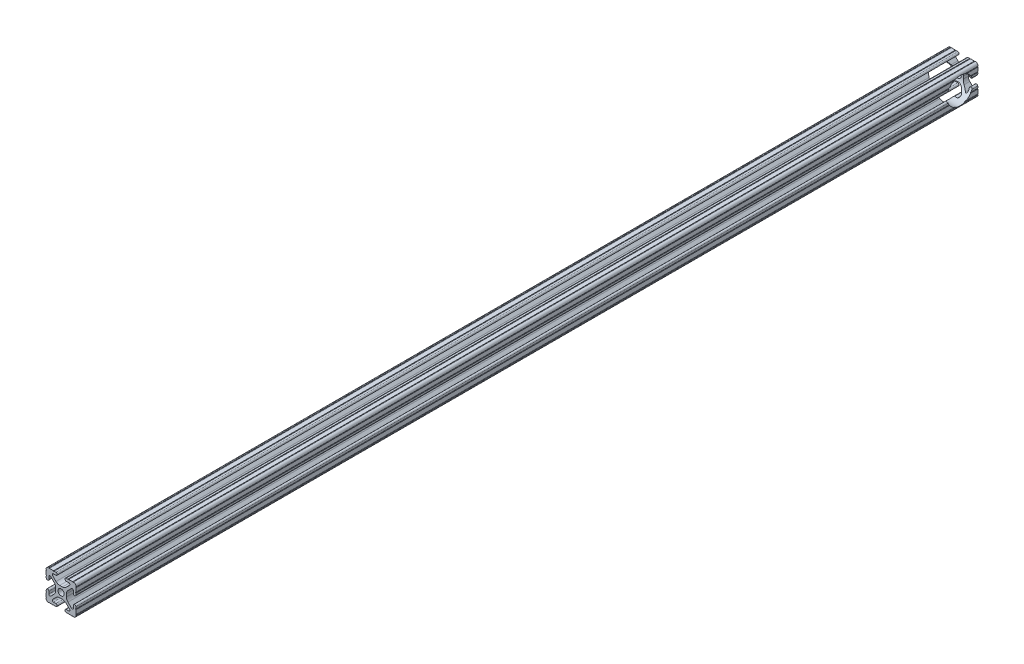
SolidWorks part; units mm, degrees
ref_plane "Front Plane" through (0, 0, 0) normal (0, 0, 1) x (1, 0, 0)
ref_plane "Top Plane" through (0, 0, 0) normal (0, 1, 0) x (1, 0, 0)
ref_plane "Right Plane" through (0, 0, 0) normal (1, 0, 0) x (0, 0, -1)
sketch "Sketch1" plane through (0, 0, 0) normal (0, 0, 1) x (1, 0, 0)
  line L0 (0, 12.7) -> (-12.7814, 12.7) construction
  line L1 (-4.5085, 0) -> (-4.5085, 2.9459)
  line L2 (-6.0437, 12.5461) -> (-10.0976, 12.6876) construction
  line L3 (-11.5616, 12.4229) -> (-4.3159, 12.1699) construction
  line L4 (-6.4364, 10.3486) -> (-6.3592, 12.5571) construction
  line L6 (-2.9459, 4.5085) -> (0, 4.5085)
  line L7 (0, 0) -> (0, 12.7) construction
  line L8 (0, 0) -> (-12.7814, 0) construction
  line L9 (0.7813, 0.7813) -> (-0.7813, -0.7813) construction
  line L10 (-2.9459, 4.5085) -> (-7.1484, 8.711)
  line L11 (-4.5085, 2.9459) -> (-8.711, 7.1484)
  line L13 (0, 0) -> (-12.7814, 12.7814) construction
  line L14 (-10.4131, 12.6987) -> (-4.3048, 12.4853)
  line L15 (-4.3048, 12.4853) -> (-4.382, 10.2769) construction
  line L16 (-4.382, 10.2769) -> (-6.4364, 10.3486)
  line L17 (-12.6987, 10.4131) -> (-12.4853, 4.3048)
  line L18 (-10.2769, 4.382) -> (-10.3486, 6.4364)
  circle A0 centre (0, 0) radius 2.6035
  arc A1 (-4.382, 10.2769) -> (-4.3048, 12.4853) centre (-4.3434, 11.3811) ccw
  arc A2 (-7.1484, 8.711) -> (-6.4364, 10.3486) centre (-6.4698, 9.3896) cw
  arc A3 (-8.711, 7.1484) -> (-10.3486, 6.4364) centre (-9.3896, 6.4698) ccw
  arc A4 (-10.2769, 4.382) -> (-12.4853, 4.3048) centre (-11.3811, 4.3434) cw
  arc A5 (-10.4131, 12.6987) -> (-12.6987, 10.4131) centre (-10.4902, 10.4902) ccw
  arc A6 (-10.4131, 12.6987) -> (-9.7821, 12.6766) centre (-10.0976, 12.6876) ccw
  arc A7 (-6.3592, 12.5571) -> (-5.7282, 12.5351) centre (-6.0437, 12.5461) ccw
  arc A8 (-12.5571, 6.3592) -> (-12.5351, 5.7282) centre (-12.5461, 6.0437) cw
  arc A9 (-12.6987, 10.4131) -> (-12.6766, 9.7821) centre (-12.6876, 10.0976) cw
  dimension "D1" = 5.207
  dimension "D5" = 14.859
  dimension "D9" = 2
  dimension "D2" = 25.4
  dimension "D12" = 0.6314
  dimension "D10" = 2.2098
  dimension "D3" = 9.017
  dimension "D4" = 9.017
  dimension "D6" = 25.4
  dimension "D7" = 6.477
  dimension "D8" = 2.2098
  dimension "D11" = 12.7
sketch "Sketch3" plane through (0, 0, 0) normal (0, 0, 1) x (1, 0, 0)
  line L0 (-2.9459, 4.5085) -> (0, 4.5085) construction
  line L1 (-2.9459, 4.5085) -> (-7.1484, 8.711) construction
  line L2 (-4.382, 10.2769) -> (-6.4364, 10.3486) construction
  line L3 (-10.4131, 12.6987) -> (-4.3048, 12.4853) construction
  line L4 (-4.5085, 0) -> (-4.5085, 2.9459) construction
  line L5 (-4.5085, 2.9459) -> (-8.711, 7.1484) construction
  line L6 (-10.2769, 4.382) -> (-10.3486, 6.4364) construction
  line L7 (-12.6987, 10.4131) -> (-12.4853, 4.3048) construction
  line L8 (-1.1153, 4.5085) -> (1.1153, 4.5085)
  line L9 (-4.2404, 5.803) -> (-7.1484, 8.711)
  line L10 (-4.382, 10.2769) -> (-6.4364, 10.3486)
  line L11 (-9.7821, 12.6766) -> (-6.3592, 12.5571)
  line L12 (-4.5085, -1.1153) -> (-4.5085, 1.1153)
  line L13 (-5.803, 4.2404) -> (-8.711, 7.1484)
  line L14 (-10.2769, 4.382) -> (-10.3486, 6.4364)
  line L15 (-12.6766, 9.7821) -> (-12.5571, 6.3592)
  line L16 (-5.7282, 12.5351) -> (-4.3048, 12.4853)
  line L17 (-12.5351, 5.7282) -> (-12.4853, 4.3048)
  line L18 (0, 0) -> (0, 12.7) construction
  line L19 (0, 0) -> (-12.7814, 0) construction
  line L20 (12.5351, 5.7282) -> (12.4853, 4.3048)
  line L21 (5.7282, 12.5351) -> (4.3048, 12.4853)
  line L22 (12.6766, 9.7821) -> (12.5571, 6.3592)
  line L23 (10.2769, 4.382) -> (10.3486, 6.4364)
  line L24 (5.803, 4.2404) -> (8.711, 7.1484)
  line L25 (4.5085, -1.1153) -> (4.5085, 1.1153)
  line L26 (9.7821, 12.6766) -> (6.3592, 12.5571)
  line L27 (4.382, 10.2769) -> (6.4364, 10.3486)
  line L28 (4.2404, 5.803) -> (7.1484, 8.711)
  line L29 (4.2404, -5.803) -> (7.1484, -8.711)
  line L30 (4.382, -10.2769) -> (6.4364, -10.3486)
  line L31 (9.7821, -12.6766) -> (6.3592, -12.5571)
  line L32 (5.803, -4.2404) -> (8.711, -7.1484)
  line L33 (10.2769, -4.382) -> (10.3486, -6.4364)
  line L34 (12.6766, -9.7821) -> (12.5571, -6.3592)
  line L35 (5.7282, -12.5351) -> (4.3048, -12.4853)
  line L36 (12.5351, -5.7282) -> (12.4853, -4.3048)
  line L37 (-12.5351, -5.7282) -> (-12.4853, -4.3048)
  line L38 (-5.7282, -12.5351) -> (-4.3048, -12.4853)
  line L39 (-12.6766, -9.7821) -> (-12.5571, -6.3592)
  line L40 (-10.2769, -4.382) -> (-10.3486, -6.4364)
  line L41 (-5.803, -4.2404) -> (-8.711, -7.1484)
  line L42 (-9.7821, -12.6766) -> (-6.3592, -12.5571)
  line L43 (-4.382, -10.2769) -> (-6.4364, -10.3486)
  line L44 (-4.2404, -5.803) -> (-7.1484, -8.711)
  line L45 (-1.1153, -4.5085) -> (1.1153, -4.5085)
  arc A0 (-10.4131, 12.6987) -> (-9.7821, 12.6766) centre (-10.0976, 12.6876) ccw construction
  arc A1 (-6.4364, 10.3486) -> (-7.1484, 8.711) centre (-6.4698, 9.3896) ccw construction
  arc A2 (-4.382, 10.2769) -> (-4.3048, 12.4853) centre (-4.3434, 11.3811) ccw construction
  arc A3 (-8.711, 7.1484) -> (-10.3486, 6.4364) centre (-9.3896, 6.4698) ccw construction
  arc A4 (-12.4853, 4.3048) -> (-10.2769, 4.382) centre (-11.3811, 4.3434) ccw construction
  arc A5 (-6.3592, 12.5571) -> (-5.7282, 12.5351) centre (-6.0437, 12.5461) ccw construction
  arc A6 (-10.4131, 12.6987) -> (-12.6987, 10.4131) centre (-10.4902, 10.4902) ccw construction
  arc A7 (-12.6766, 9.7821) -> (-12.6987, 10.4131) centre (-12.6876, 10.0976) ccw construction
  arc A8 (-12.5351, 5.7282) -> (-12.5571, 6.3592) centre (-12.5461, 6.0437) ccw construction
  arc A9 (-10.4131, 12.6987) -> (-9.7821, 12.6766) centre (-10.0976, 12.6876) ccw
  arc A10 (-6.4364, 10.3486) -> (-7.1484, 8.711) centre (-6.4698, 9.3896) ccw
  arc A11 (-4.382, 10.2769) -> (-4.3048, 12.4853) centre (-4.3434, 11.3811) ccw
  arc A12 (-8.711, 7.1484) -> (-10.3486, 6.4364) centre (-9.3896, 6.4698) ccw
  arc A13 (-12.4853, 4.3048) -> (-10.2769, 4.382) centre (-11.3811, 4.3434) ccw
  arc A14 (-6.3592, 12.5571) -> (-5.7282, 12.5351) centre (-6.0437, 12.5461) ccw
  arc A15 (-10.4131, 12.6987) -> (-12.6987, 10.4131) centre (-10.4902, 10.4902) ccw
  arc A16 (-12.6766, 9.7821) -> (-12.6987, 10.4131) centre (-12.6876, 10.0976) ccw
  arc A17 (-12.5351, 5.7282) -> (-12.5571, 6.3592) centre (-12.5461, 6.0437) ccw
  arc A18 (-1.1153, 4.5085) -> (-4.2404, 5.803) centre (-1.1153, 8.9281) cw
  arc A19 (4.5085, 1.1153) -> (5.803, 4.2404) centre (8.9281, 1.1153) cw
  arc A20 (1.1153, 4.5085) -> (4.2404, 5.803) centre (1.1153, 8.9281) ccw
  arc A21 (-4.5085, 1.1153) -> (-5.803, 4.2404) centre (-8.9281, 1.1153) ccw
  arc A22 (12.5351, 5.7282) -> (12.5571, 6.3592) centre (12.5461, 6.0437) cw
  arc A23 (12.6766, 9.7821) -> (12.6987, 10.4131) centre (12.6876, 10.0976) cw
  arc A24 (10.4131, 12.6987) -> (12.6987, 10.4131) centre (10.4902, 10.4902) cw
  arc A25 (6.3592, 12.5571) -> (5.7282, 12.5351) centre (6.0437, 12.5461) cw
  arc A26 (12.4853, 4.3048) -> (10.2769, 4.382) centre (11.3811, 4.3434) cw
  arc A27 (8.711, 7.1484) -> (10.3486, 6.4364) centre (9.3896, 6.4698) cw
  arc A28 (4.382, 10.2769) -> (4.3048, 12.4853) centre (4.3434, 11.3811) cw
  arc A29 (6.4364, 10.3486) -> (7.1484, 8.711) centre (6.4698, 9.3896) cw
  arc A30 (10.4131, 12.6987) -> (9.7821, 12.6766) centre (10.0976, 12.6876) cw
  arc A31 (10.4131, -12.6987) -> (9.7821, -12.6766) centre (10.0976, -12.6876) ccw
  arc A32 (6.4364, -10.3486) -> (7.1484, -8.711) centre (6.4698, -9.3896) ccw
  arc A33 (4.382, -10.2769) -> (4.3048, -12.4853) centre (4.3434, -11.3811) ccw
  arc A34 (8.711, -7.1484) -> (10.3486, -6.4364) centre (9.3896, -6.4698) ccw
  arc A35 (12.4853, -4.3048) -> (10.2769, -4.382) centre (11.3811, -4.3434) ccw
  arc A36 (6.3592, -12.5571) -> (5.7282, -12.5351) centre (6.0437, -12.5461) ccw
  arc A37 (10.4131, -12.6987) -> (12.6987, -10.4131) centre (10.4902, -10.4902) ccw
  arc A38 (12.6766, -9.7821) -> (12.6987, -10.4131) centre (12.6876, -10.0976) ccw
  arc A39 (12.5351, -5.7282) -> (12.5571, -6.3592) centre (12.5461, -6.0437) ccw
  arc A40 (-4.5085, -1.1153) -> (-5.803, -4.2404) centre (-8.9281, -1.1153) cw
  arc A41 (1.1153, -4.5085) -> (4.2404, -5.803) centre (1.1153, -8.9281) cw
  arc A42 (4.5085, -1.1153) -> (5.803, -4.2404) centre (8.9281, -1.1153) ccw
  arc A43 (-1.1153, -4.5085) -> (-4.2404, -5.803) centre (-1.1153, -8.9281) ccw
  arc A44 (-12.5351, -5.7282) -> (-12.5571, -6.3592) centre (-12.5461, -6.0437) cw
  arc A45 (-12.6766, -9.7821) -> (-12.6987, -10.4131) centre (-12.6876, -10.0976) cw
  arc A46 (-10.4131, -12.6987) -> (-12.6987, -10.4131) centre (-10.4902, -10.4902) cw
  arc A47 (-6.3592, -12.5571) -> (-5.7282, -12.5351) centre (-6.0437, -12.5461) cw
  arc A48 (-12.4853, -4.3048) -> (-10.2769, -4.382) centre (-11.3811, -4.3434) cw
  arc A49 (-8.711, -7.1484) -> (-10.3486, -6.4364) centre (-9.3896, -6.4698) cw
  arc A50 (-4.382, -10.2769) -> (-4.3048, -12.4853) centre (-4.3434, -11.3811) cw
  arc A51 (-6.4364, -10.3486) -> (-7.1484, -8.711) centre (-6.4698, -9.3896) cw
  arc A52 (-10.4131, -12.6987) -> (-9.7821, -12.6766) centre (-10.0976, -12.6876) cw
  circle A53 centre (0, 0) radius 2.6035 construction
  circle A54 centre (0, 0) radius 2.6035
  point P135 (4.5085, 0)
  dimension "D2" = 4.4196
extrude "Extrude1" add sketch "Sketch3" along normal mid plane 760
ref_plane "Plane1" through (12.4853, 4.3048, 380) normal (0.0349, 0.9994, 0) x (0.9994, -0.0349, 0)
sketch "Sketch5" plane through (4.5085, 0, 0) normal (1, 0, 0) x (0, 0, -1)
  line L1 (380, -1.1153) -> (380, 1.1153) construction
  circle A0 centre (365, 0) radius 11
  dimension "D1" = 22
  dimension "D2" = 15
extrude "Cut-Extrude2" cut sketch "Sketch5" against normal through all and the other way through all
equation "\"D10@Sketch1\" = \"D8@Sketch1\""
equation "\"D11@Sketch1\" = \"D6@Sketch1\"/2"
equation "\"D12@Sketch1\" = \"D8@Sketch1\"/3.5"
equation "\"D2@Sketch3\" = \"D8@Sketch1\"*2"
